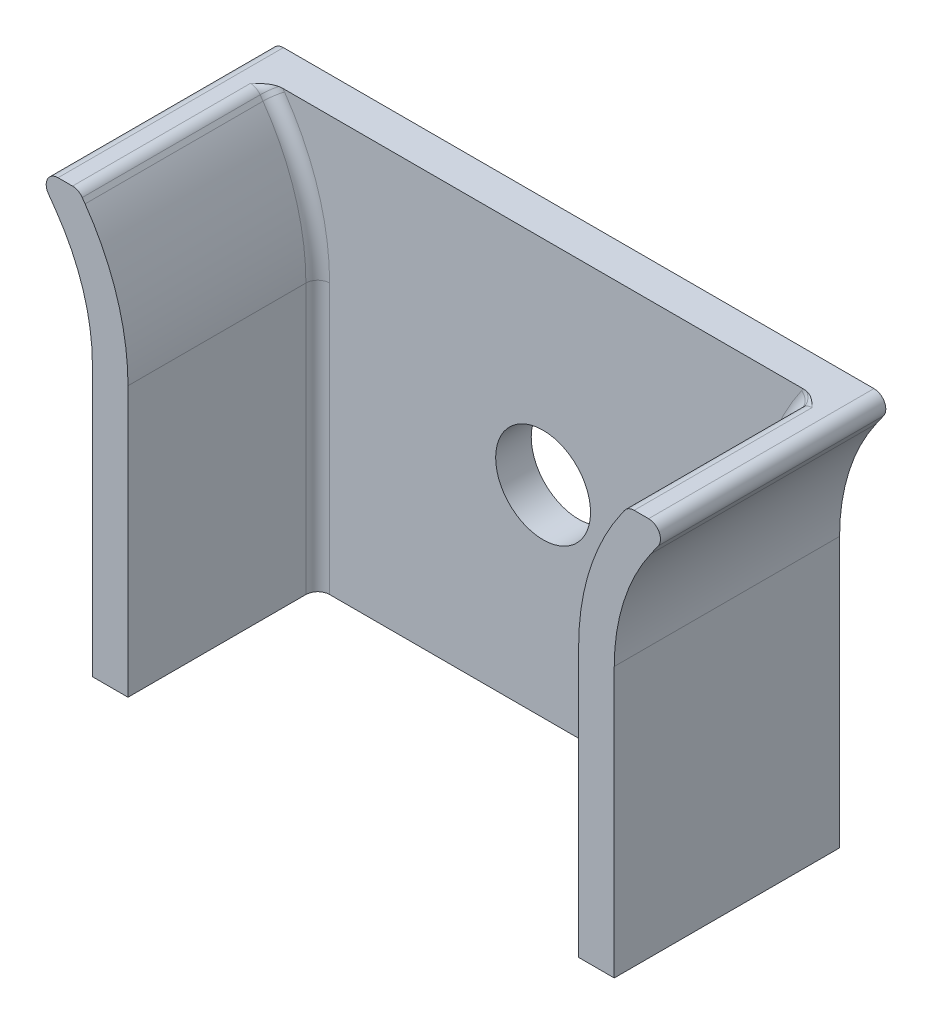
SolidWorks part; units mm, degrees
ref_plane "Front Plane" through (0, 0, 0) normal (0, 0, 1) x (1, 0, 0)
ref_plane "Top Plane" through (0, 0, 0) normal (0, 1, 0) x (1, 0, 0)
ref_plane "Right Plane" through (0, 0, 0) normal (1, 0, 0) x (0, 0, -1)
sketch "Sketch1" plane through (0, 0, 0) normal (0, 0, 1) x (1, 0, 0)
  line L9 (-24.3617, 36.7114) -> (-22.617, 34.2197)
  line L10 (-19, 22.7481) -> (-19, 0)
  line L11 (-24.3617, 36.7114) -> (24.3617, 36.7114)
  line L12 (-19, 0) -> (19, 0)
  line L15 (0, -55) -> (0, 55) construction
  line L16 (19, 22.7481) -> (19, 0)
  line L17 (-26.8192, 34.9907) -> (-25.0744, 32.4989)
  line L18 (24.3617, 36.7114) -> (22.617, 34.2197)
  line L19 (-22, 22.7481) -> (-22, 0)
  line L20 (22, 22.7481) -> (22, 0)
  line L21 (26.8192, 34.9907) -> (25.0744, 32.4989)
  line L22 (22, 0) -> (-22, 0)
  line L23 (-26.8192, 34.9907) -> (26.8192, 34.9907)
  arc A3 (-19, 22.7481) -> (-22.617, 34.2197) centre (-39, 22.7481) ccw
  arc A5 (19, 22.7481) -> (22.617, 34.2197) centre (39, 22.7481) cw
  arc A6 (-22, 22.7481) -> (-25.0744, 32.4989) centre (-39, 22.7481) ccw
  arc A7 (22, 22.7481) -> (25.0744, 32.4989) centre (39, 22.7481) cw
  point P16 (0, 0)
  point P18 (0, 36.7114)
  point P28 (0, 0)
  dimension "D1" = 20
  dimension "D2" = 38
  dimension "D3" = 22.7481
  dimension "D4" = 5.3617
  dimension "D5" = 36.7114
  dimension "D6" = 3
extrude "Boss-Extrude1" add sketch "Sketch1" along normal blind 3 contours L16 A5 L18 L23 L9 A3 L10 L12 | A6 L19 L22 L10 A3 L9 L23 L17 | L20 A7 L21 L23 L18 A5 L16 L22 region at (0, 17.8421, 0) region at (-21.0735, 17.9174, 0) region at (21.0735, 17.9174, 0)
sketch "Sketch2" plane through (0, 0, 3) normal (0, 0, 1) x (1, 0, 0)
  line L4 (-26.8192, 34.9907) -> (-23.1568, 34.9907)
  line L5 (-22, 0) -> (-19, 0)
  line L6 (-19, 22.7481) -> (-19, 0)
  line L7 (-24.3617, 36.7114) -> (-22.617, 34.2197)
  line L8 (-19, 22.7481) -> (-19, 0)
  line L9 (-24.3617, 36.7114) -> (-22.617, 34.2197)
  line L10 (0, -1.65) -> (0, 1.65) construction
  line L11 (22, 22.7481) -> (22, 0)
  line L12 (26.8192, 34.9907) -> (25.0744, 32.4989)
  line L13 (24.3617, 36.7114) -> (22.617, 34.2197)
  line L14 (-22, 0) -> (22, 0)
  line L15 (22, 0) -> (22, 22.7481)
  line L16 (25.0744, 32.4989) -> (26.8192, 34.9907)
  line L17 (26.8192, 34.9907) -> (-26.8192, 34.9907)
  line L18 (-26.8192, 34.9907) -> (-25.0744, 32.4989)
  line L19 (-22, 22.7481) -> (-22, 0)
  line L20 (-22, 0) -> (22, 0)
  line L21 (22, 0) -> (22, 22.7481)
  line L22 (25.0744, 32.4989) -> (26.8192, 34.9907)
  line L23 (26.8192, 34.9907) -> (-26.8192, 34.9907)
  line L24 (-26.8192, 34.9907) -> (-25.0744, 32.4989)
  line L25 (-22, 22.7481) -> (-22, 0)
  line L26 (19, 22.7481) -> (19, 0)
  line L27 (26.8192, 34.9907) -> (23.1568, 34.9907)
  line L28 (22, 0) -> (19, 0)
  arc A2 (22, 22.7481) -> (25.0744, 32.4989) centre (39, 22.7481) cw
  arc A3 (-19, 22.7481) -> (-22.617, 34.2197) centre (-39, 22.7481) ccw
  arc A4 (-19, 22.7481) -> (-22.617, 34.2197) centre (-39, 22.7481) ccw
  arc A5 (19, 22.7481) -> (22.617, 34.2197) centre (39, 22.7481) cw
  arc A6 (25.0744, 32.4989) -> (22, 22.7481) centre (39, 22.7481) ccw
  arc A7 (-22, 22.7481) -> (-25.0744, 32.4989) centre (-39, 22.7481) ccw
  arc A8 (25.0744, 32.4989) -> (22, 22.7481) centre (39, 22.7481) ccw
  arc A9 (-22, 22.7481) -> (-25.0744, 32.4989) centre (-39, 22.7481) ccw
  line M12 (-22, 0) -> (22, 0)
  line M13 (22, 0) -> (22, 22.7481)
  arc M14 (22, 22.7481) -> (25.0744, 32.4989) centre (39, 22.7481) cw
  line M15 (25.0744, 32.4989) -> (26.8192, 34.9907)
  line M16 (26.8192, 34.9907) -> (-26.8192, 34.9907)
  line M17 (-26.8192, 34.9907) -> (-25.0744, 32.4989)
  arc M18 (-25.0744, 32.4989) -> (-22, 22.7481) centre (-39, 22.7481) cw
  line M19 (-22, 22.7481) -> (-22, 0)
  dimension "D1" = 3
  dimension "D2" = 0
extrude "Boss-Extrude2" add sketch "Sketch2" along normal blind 16 contours L8 A4 L9 M16 M17 M18 M19 M12 | A5 L26 L20 L13 M13 M14 M15 M16 region at (-21.0735, 17.9174, 3) region at (21.0735, 17.9174, 3)
fillet "Fillet1" radius 1 4 edges at (23.1568, 34.9907, 11) (-23.1568, 34.9907, 11) (26.8192, 34.9907, 9.5) (-26.8192, 34.9907, 9.5)
fillet "Fillet2" radius 1 8 edges at (23.2156, 34.8777, 3) (22.7376, 34.392, 3) (19.9257, 28.7622, 3) (-23.2156, 34.8777, 3) (-22.7376, 34.392, 3) (-19.9257, 28.7622, 3) (19, 11.3741, 3) (-19, 11.3741, 3)
sketch "Sketch3" plane through (0, 0, 0) normal (0, 0, -1) x (-1, 0, 0)
  circle A0 centre (0, 17) radius 4
  point P0 (0, 17)
extrude "Cut-Extrude1" cut sketch "Sketch3" against normal up to surface (3 mm away) up to face at (0, 23.2061, 3)
